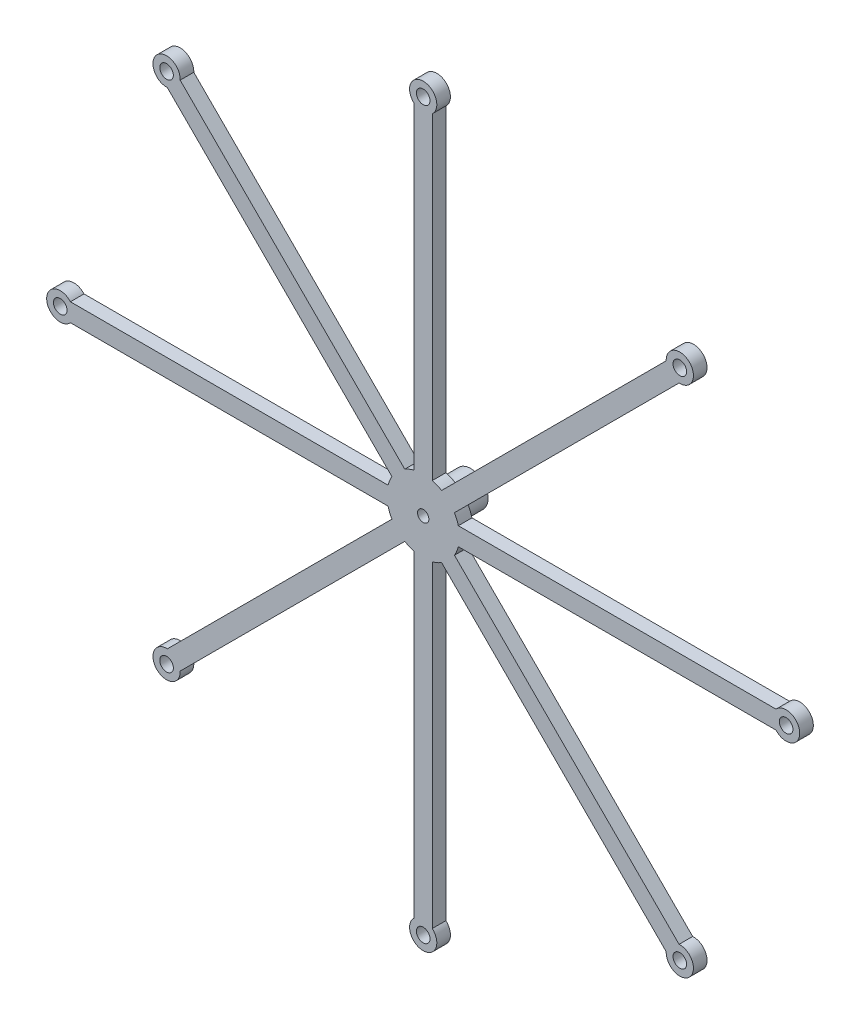
SolidWorks part; units mm, degrees
ref_plane "前视基准面" through (0, 0, 0) normal (0, 0, 1) x (1, 0, 0)
ref_plane "上视基准面" through (0, 0, 0) normal (0, 1, 0) x (1, 0, 0)
ref_plane "右视基准面" through (0, 0, 0) normal (1, 0, 0) x (0, 0, -1)
other "Configuration Table"
ref_axis "基准轴1" through (0, 0, 0) along (0, 0, 1)
sketch "草图1" plane through (0, 0, 0) normal (0, 0, 1) x (1, 0, 0)
  circle A0 centre (0, 0) radius 8
  dimension "D1" = 16
extrude "凸台-拉伸1" add sketch "草图1" along normal blind 3
sketch "草图2" plane through (0, 0, 3) normal (0, 0, 1) x (1, 0, 0)
  line L0 (0, 0) -> (80, 0) construction
  line L1 (77.7639, 2) -> (7.746, 2)
  line L2 (7.746, -2) -> (77.7639, -2)
  circle A0 centre (80, 0) radius 1.5
  circle A1 centre (80, 0) radius 3
  circle A2 centre (0, 0) radius 8 construction
  circle M6 centre (0, 0) radius 8
  dimension "D2" = 6
  dimension "D3" = 3
  dimension "D1" = 4
  dimension "D4" = 80
extrude "凸台-拉伸-辐条" add sketch "草图2" against normal up to surface (3 mm away) contours L0 A1 L1 M6 | L0 L2 A1 M6 | A1 A0 region at (42.5783, 1.0024, 3) region at (42.5783, -1.0024, 3) region at (77.2768, 1.0402, 3) up to face at (8, 0, 0)
pattern_circular "阵列(圆周)3" count 8 over 360 about axis through (0, 0, 0) along (0, 0, 1) of "凸台-拉伸-辐条"
sketch "草图3" plane through (0, 0, 0) normal (0, 0, -1) x (-1, 0, 0)
  circle A0 centre (0, 0) radius 3.8
  dimension "D1" = 7.6
extrude "凸台-拉伸3" add sketch "草图3" along normal blind 7.5
sketch "草图4" plane through (0, 0, -7.5) normal (0, 0, -1) x (-1, 0, 0)
  circle A0 centre (0, 0) radius 1.25
  dimension "D1" = 2.5
extrude "切除-拉伸1" cut sketch "草图4" against normal through all
